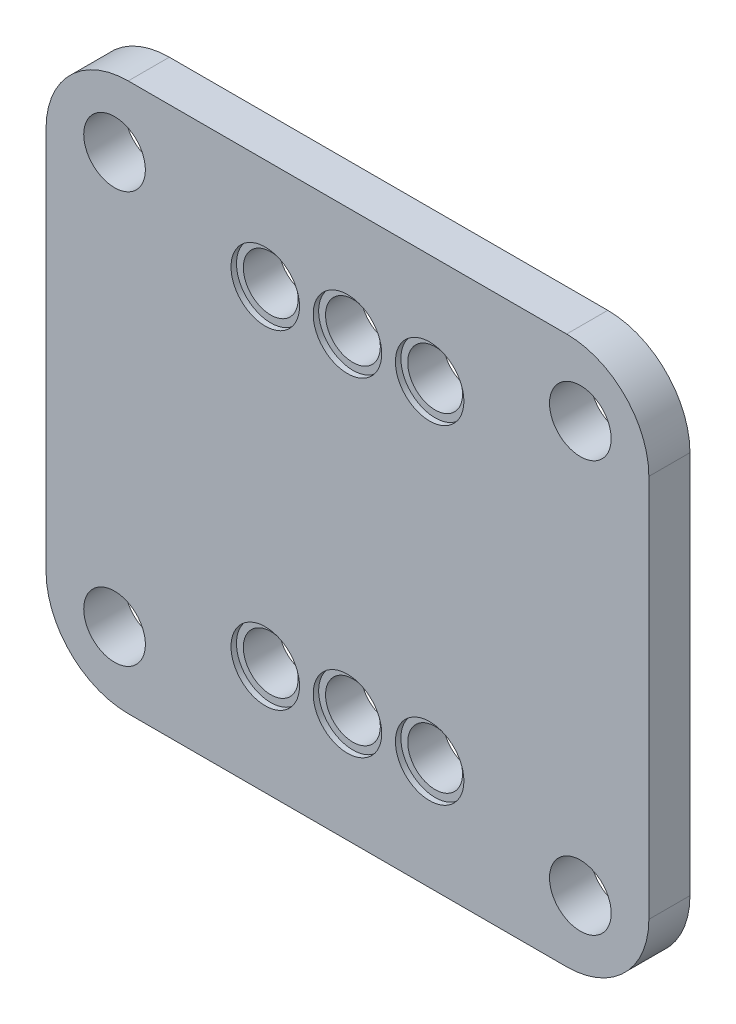
SolidWorks part; units mm, degrees
ref_plane "Plan de face" through (0, 0, 0) normal (0, 0, 1) x (1, 0, 0)
ref_plane "Plan de dessus" through (0, 0, 0) normal (0, 1, 0) x (1, 0, 0)
ref_plane "Plan de droite" through (0, 0, 0) normal (1, 0, 0) x (0, 0, -1)
sketch "Esquisse2" plane through (0, 0, 0) normal (0, 0, 1) x (1, 0, 0)
  line L1 (0, 0) -> (44, 0)
  line L2 (0, 0) -> (0, 40)
  line L3 (0, 40) -> (44, 40)
  line L4 (44, 0) -> (44, 40)
  dimension "D1" = 44
  dimension "D2" = 40
extrude "Boss.-Extru.1" add sketch "Esquisse2" along normal blind 3
sketch "Esquisse3" plane through (0, 0, 3) normal (0, 0, 1) x (1, 0, 0)
  line L0 (22, 0) -> (22, 40) construction
  line L1 (0, 0) -> (44, 0) construction
  line L2 (44, 40) -> (0, 40) construction
  line L3 (0, 20) -> (44, 20) construction
  line L4 (0, 40) -> (0, 0) construction
  line L5 (44, 0) -> (44, 40) construction
  line L6 (16, 32) -> (22, 32) construction
  line L7 (16, 8) -> (22, 8) construction
  circle A0 centre (22, 32) radius 2
  circle A1 centre (16, 32) radius 2
  circle A2 centre (28, 32) radius 2
  circle A3 centre (28, 8) radius 2
  circle A4 centre (16, 8) radius 2
  circle A5 centre (22, 8) radius 2
  circle A6 centre (5, 35) radius 2.25
  circle A7 centre (5, 5) radius 2.25
  circle A8 centre (39, 5) radius 2.25
  circle A9 centre (39, 35) radius 2.25
  dimension "D1" = 4
  dimension "D2" = 24
  dimension "D3" = 6
  dimension "D4" = 4.5
  dimension "D5" = 30
  dimension "D6" = 34
extrude "Enlèv. mat.-Extru.1" cut sketch "Esquisse3" against normal through all both and the other way through all
fillet "Congé1" radius 6 4 edges at (0, 40, 1.5) (0, 0, 1.5) (44, 0, 1.5) (44, 40, 1.5)
sketch "Esquisse4" plane through (0, 0, 3) normal (0, 0, 1) x (1, 0, 0)
  circle A0 centre (16, 8) radius 2.5
  circle A1 centre (22, 8) radius 2.5
  circle A2 centre (28, 8) radius 2.5
  circle A3 centre (28, 32) radius 2.5
  circle A4 centre (22, 32) radius 2.5
  circle A5 centre (16, 32) radius 2.5
  dimension "D1" = 5
extrude "Enlèv. mat.-Extru.2" cut sketch "Esquisse4" against normal blind 0.4
